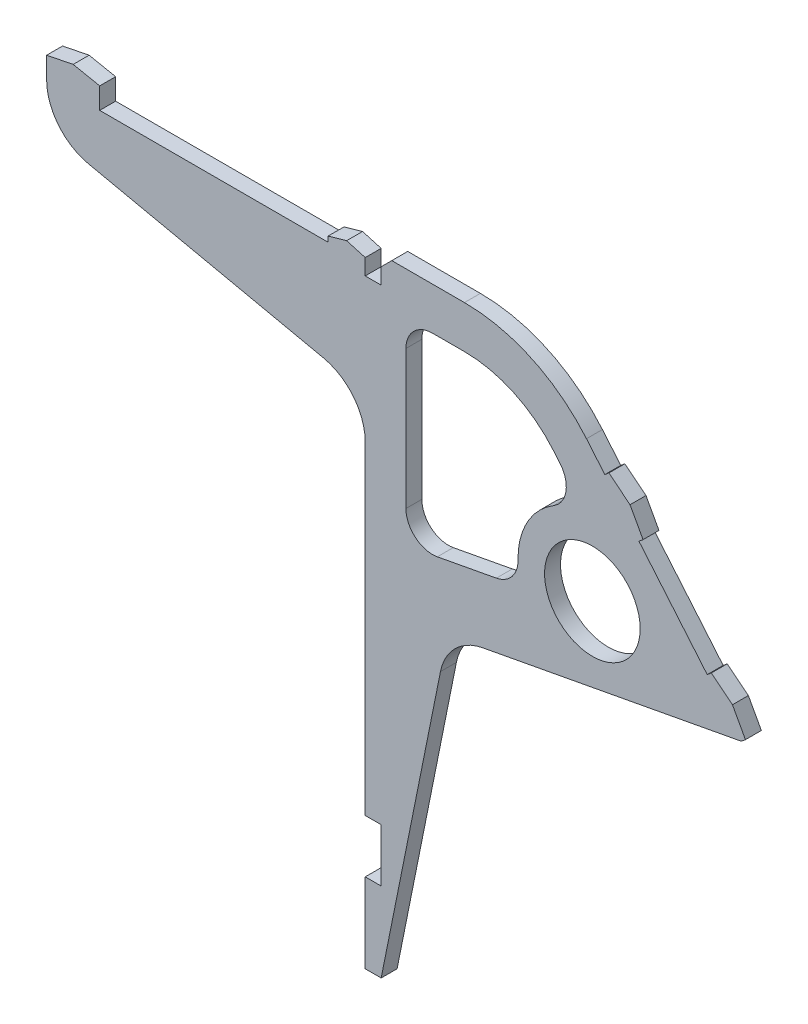
SolidWorks part; units mm, degrees
material "Stal węglowa"
ref_plane "Front" through (0, 0, 0) normal (0, 0, 1) x (1, 0, 0)
ref_plane "Top" through (0, 0, 0) normal (0, 1, 0) x (1, 0, 0)
ref_plane "Right" through (0, 0, 0) normal (1, 0, 0) x (0, 0, -1)
sketch "Szkic1" plane through (0, 0, 0) normal (0, 0, 1) x (1, 0, 0)
  line L0 (-39.7759, -56.3421) -> (-42.7759, -56.3421)
  line L1 (-92.7759, 33.6579) -> (-49.7759, 33.6579)
  line L2 (-39.7759, 31.6579) -> (-39.7759, 34.6579)
  line L3 (-42.7759, 4.5872) -> (-42.7759, -56.3421)
  line L4 (-39.7759, -66.3421) -> (-39.7759, -56.3421)
  line L5 (-42.7759, -66.3421) -> (-42.7759, -81.3421)
  line L6 (-39.7759, -81.3421) -> (-42.7759, -81.3421)
  line L7 (-39.7759, -66.3421) -> (-42.7759, -66.3421)
  line L8 (-39.7759, 31.6579) -> (-42.7759, 31.6579)
  line L9 (-20.6419, -17.9261) -> (28.0587, -8.8183)
  line L10 (21.6308, -1.1579) -> (8.7751, 14.163)
  line L11 (-92.7759, 33.6579) -> (-92.7759, 37.6579)
  line L12 (-102.7759, 33.6579) -> (-102.7759, 37.6579)
  line L13 (-42.7759, 31.6579) -> (-42.7759, 34.6579)
  line L14 (-49.7759, 33.6579) -> (-49.7759, 34.6579)
  line L15 (-39.7759, -81.3421) -> (-28.6075, -25.7848)
  line L16 (-24.0896, 36.6579) -> (-37.7759, 36.6579)
  line L17 (-37.7759, 36.6579) -> (-39.7759, 34.6579)
  line L18 (-102.7759, 37.6579) -> (-97.7759, 38.6579)
  line L19 (-97.7759, 38.6579) -> (-92.7759, 37.6579)
  line L20 (-46.2759, 35.6579) -> (-49.7759, 34.6579)
  line L21 (-42.7759, 34.6579) -> (-46.2759, 35.6579)
  line L22 (28.8277, -8.1731) -> (28.0587, -8.8183)
  line L23 (9.544, 14.8082) -> (8.7751, 14.163)
  line L24 (3.1162, 22.4687) -> (2.3472, 21.8235)
  line L25 (22.3998, -0.5126) -> (21.6308, -1.1579)
  line L26 (2.3472, 21.8235) -> (-1.1083, 25.9416)
  line L27 (26.3798, -3.7001) -> (28.8277, -8.1731)
  line L28 (22.3998, -0.5126) -> (26.3798, -3.7001)
  line L29 (7.0962, 19.2813) -> (9.544, 14.8082)
  line L30 (3.1162, 22.4687) -> (7.0962, 19.2813)
  line L31 (-35.1137, -2.4432) -> (-35.1137, 23.6579)
  line L32 (-29.1946, -7.358) -> (-18.0774, -5.2789)
  line L33 (-50.671, 14.3632) -> (-94.8808, 23.882)
  line L34 (-24.0896, 28.6579) -> (-30.1137, 28.6579)
  line L35 (-6.0821, 19.4234) -> (-7.2367, 20.7993)
  circle A0 centre (0, 0) radius 9
  arc A1 (-20.6419, -17.9261) -> (-28.6075, -25.7848) centre (-18.8036, -27.7557) ccw
  arc A2 (-1.1083, 25.9416) -> (-24.0896, 36.6579) centre (-24.0896, 6.6579) ccw
  arc A3 (-35.1137, -2.4432) -> (-29.1946, -7.358) centre (-30.1137, -2.4432) ccw
  arc A4 (-102.7759, 33.6579) -> (-94.8808, 23.882) centre (-92.7759, 33.6579) ccw
  arc A5 (-42.7759, 4.5872) -> (-50.671, 14.3632) centre (-52.7759, 4.5872) ccw
  arc A6 (-7.3038, 11.9438) -> (-13.9974, -0.2683) centre (0, 0) ccw
  arc A7 (-7.3038, 11.9438) -> (-6.0821, 19.4234) centre (-9.9124, 16.2094) ccw
  arc A8 (-30.1137, 28.6579) -> (-35.1137, 23.6579) centre (-30.1137, 23.6579) ccw
  arc A9 (-18.0774, -5.2789) -> (-13.9974, -0.2683) centre (-18.9965, -0.3641) ccw
  arc A10 (-7.2367, 20.7993) -> (-24.0896, 28.6579) centre (-24.0896, 6.6579) ccw
extrude "Dodanie-wyciągnięcie1" add sketch "Szkic1" along normal blind 3
